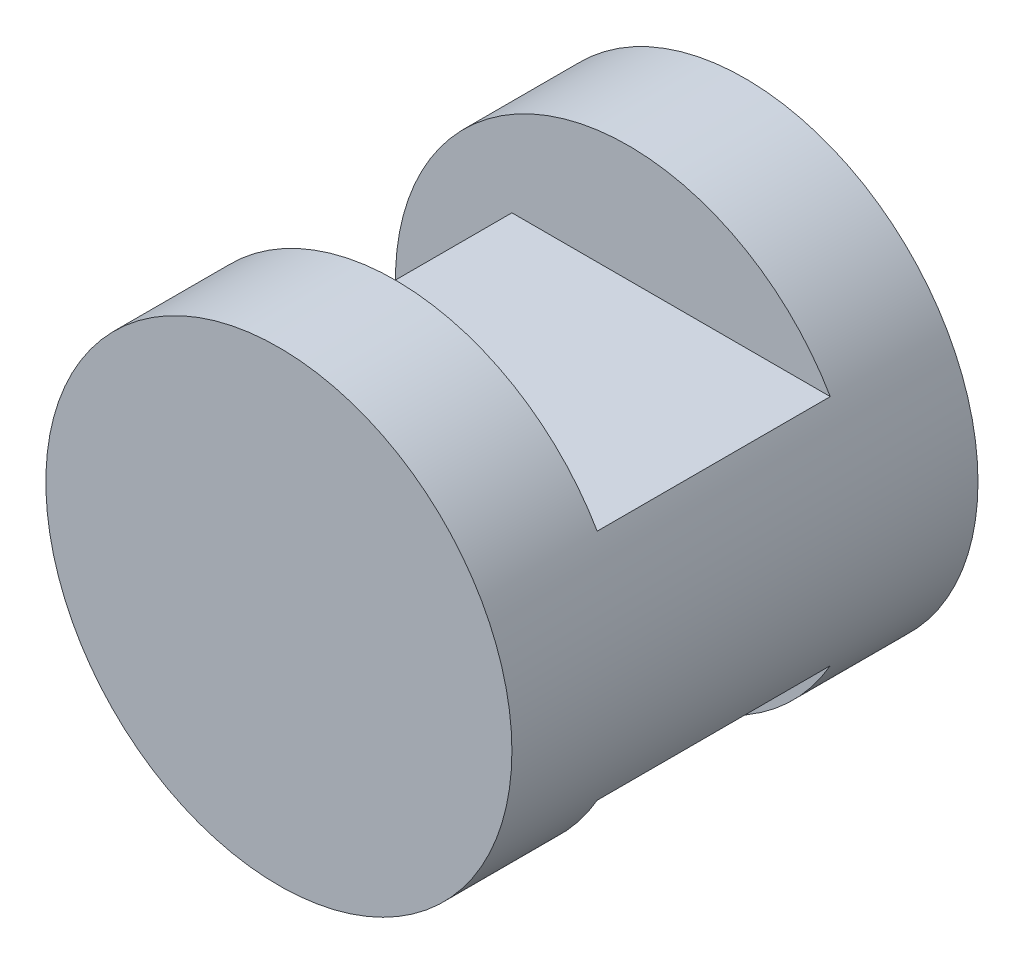
SolidWorks part; units mm, degrees
ref_plane "Front Plane" through (0, 0, 0) normal (0, 0, 1) x (1, 0, 0)
ref_plane "Top Plane" through (0, 0, 0) normal (0, 1, 0) x (1, 0, 0)
ref_plane "Right Plane" through (0, 0, 0) normal (1, 0, 0) x (0, 0, -1)
sketch "Sketch1" plane through (0, 0, 0) normal (0, 0, 1) x (1, 0, 0)
  circle A0 centre (0, 0) radius 20
  dimension "D1" = 40
extrude "Boss-Extrude1" add sketch "Sketch1" along normal blind 40
sketch "Sketch2" plane through (0, 0, 0) normal (0, 1, 0) x (1, 0, 0)
  line L0 (-20, 0) -> (-20, -40) construction
  line L1 (-20, -10) -> (-10, -10)
  line L2 (-20, -10) -> (-20, -30)
  line L3 (-20, -30) -> (-10, -30)
  line L4 (-10, -10) -> (-10, -30)
  dimension "D1" = 10
  dimension "D2" = 20
  dimension "D3" = 10
extrude "Cut-Extrude1" cut sketch "Sketch2" against normal blind 40 and the other way blind 40
sketch "Sketch3" plane through (0, 0, 0) normal (1, 0, 0) x (0, 0, -1)
  line L0 (0, 20) -> (-40, 20) construction
  line L1 (-30, 20) -> (-10, 20)
  line L2 (-30, 20) -> (-30, 10)
  line L3 (-30, 10) -> (-10, 10)
  line L4 (-10, 20) -> (-10, 10)
  line L5 (-10, 17.3205) -> (-10, -17.3205) construction
  line L6 (-40, -20) -> (0, -20) construction
  line L7 (-30, -20) -> (-10, -20)
  line L8 (-30, -20) -> (-30, -10)
  line L9 (-30, -10) -> (-10, -10)
  line L10 (-10, -20) -> (-10, -10)
  dimension "D1" = 10
  dimension "D2" = 20
  dimension "D3" = 20
  dimension "D4" = 10
extrude "Cut-Extrude2" cut sketch "Sketch3" against normal blind 40 and the other way blind 40
